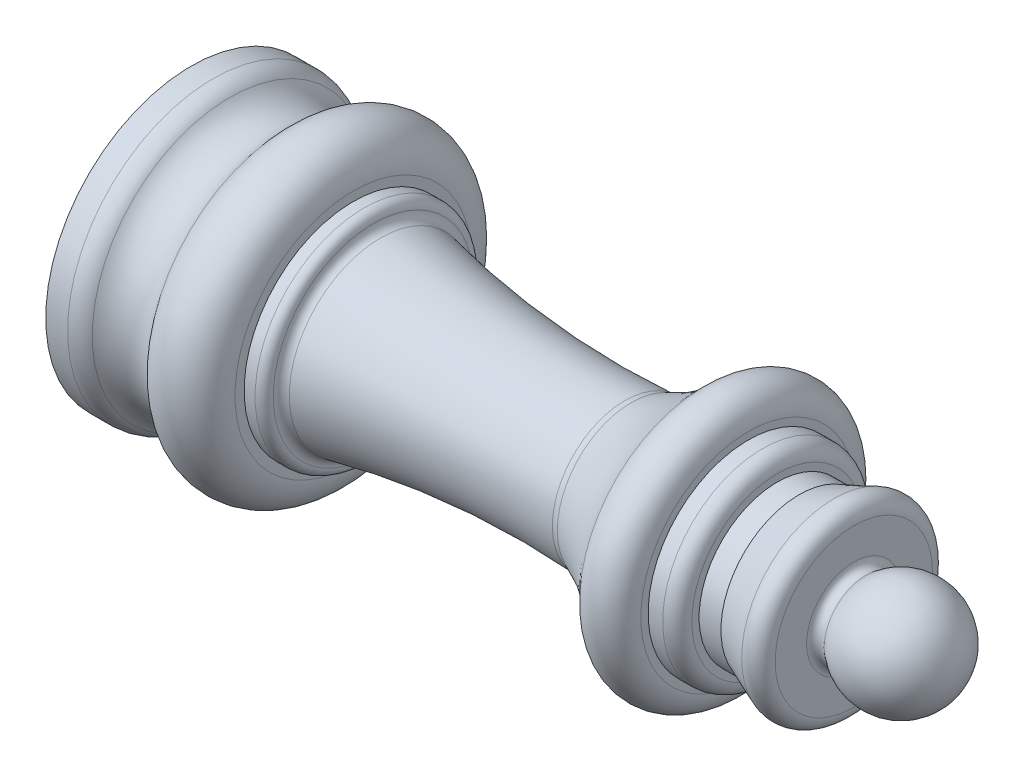
SolidWorks part; units mm, degrees
ref_plane "前基準面" through (0, 0, 0) normal (0, 0, 1) x (1, 0, 0)
ref_plane "上基準面" through (0, 0, 0) normal (0, 1, 0) x (1, 0, 0)
ref_plane "右基準面" through (0, 0, 0) normal (1, 0, 0) x (0, 0, -1)
sketch "草圖1" plane through (0, 0, 0) normal (0, 0, 1) x (1, 0, 0)
  line L0 (0, 0) -> (-114.0071, 0) construction
  line L3 (-14, 6.4807) -> (-14, 13.75)
  line L4 (-14, 13.75) -> (-21.5, 10.75)
  line L5 (-21.5, 10.75) -> (-24.5, 10.75)
  line L6 (-24.5, 10.75) -> (-24.5, 13.75)
  line L10 (-105, 0) -> (-105, 20)
  line L11 (-105, 20) -> (-102, 20)
  line L12 (0, 0) -> (-105, 0)
  line L14 (-82.75, 15) -> (-82.75, 16.25)
  line L16 (-82.75, 15) -> (-81.25, 15)
  line L20 (-24.5, 13.75) -> (-28.5, 13.75)
  line L25 (-28.5, 13.75) -> (-28.5, 14.75)
  arc A0 (-45, 10) -> (-79.0118, 12.5277) centre (-52.8282, 134.7546) cw
  arc A1 (-99.6934, 18.9183) -> (-102, 20) centre (-102, 17) ccw
  arc A3 (-80, 13.75) -> (-81.25, 15) centre (-81.25, 13.75) ccw
  arc A4 (-80, 13.75) -> (-79.0118, 12.5277) centre (-78.75, 13.75) ccw
  arc A5 (-82.75, 16.25) -> (-91.7996, 19.1827) centre (-87.75, 16.25) ccw
  arc A9 (0, 0) -> (-12.3529, 5.7183) centre (-7.5, 0) ccw
  arc A10 (-14, 6.4807) -> (-12.3529, 5.7183) centre (-13, 6.4807) ccw
  arc A12 (-28.5, 14.75) -> (-34.6375, 17.0175) centre (-31.9998, 14.7169) ccw
  arc A13 (-34.6375, 17.0175) -> (-45, 10) centre (-53.1009, 33.122) cw
  arc A14 (-99.6934, 18.9183) -> (-91.7996, 19.1827) centre (-95.8492, 22.1154) ccw
  point P4 (-30.7869, 18)
  point P26 (-99, 20)
  dimension "D14" = 125
  dimension "D17" = 3
  dimension "D20" = 25
  dimension "D22" = 1.25
  dimension "D21" = 1.25
  dimension "D24" = 1.25
  dimension "D25" = 32.5
  dimension "D11" = 5
  dimension "D12" = 5
  dimension "D33" = 45
  dimension "D28" = 15
  dimension "D31" = 24.5
  dimension "D4" = 1
  dimension "D36" = 14
  dimension "D6" = 36
  dimension "D35" = 3.5
  dimension "D3" = 27.5
  dimension "D5" = 3
  dimension "D7" = 7.5
  dimension "D8" = 105
  dimension "D9" = 4
  dimension "D10" = 21.5
  dimension "D13" = 40
  dimension "D16" = 3
  dimension "D19" = 40
  dimension "D23" = 27.5
  dimension "D26" = 1.5
  dimension "D27" = 30
  dimension "D30" = 27.5
  dimension "D32" = 6
  dimension "D34" = 20
  dimension "D37" = 1
revolve "旋轉1" add sketch "草圖1" angle 360 about L0
revolve "旋轉3" add sketch "草圖1<3>" angle 360 about L0
sketch "草圖1<3>" plane through (0, 0, 0) normal (0, 0, 1) x (1, 0, 0) same geometry as "草圖1"
fillet "圓角1" radius 2 2 edges at (-24.5, 0, -13.75) (-14, 0, -13.75)
fillet "圓角3" radius 3 1 edges at (-45, 0, -10)
